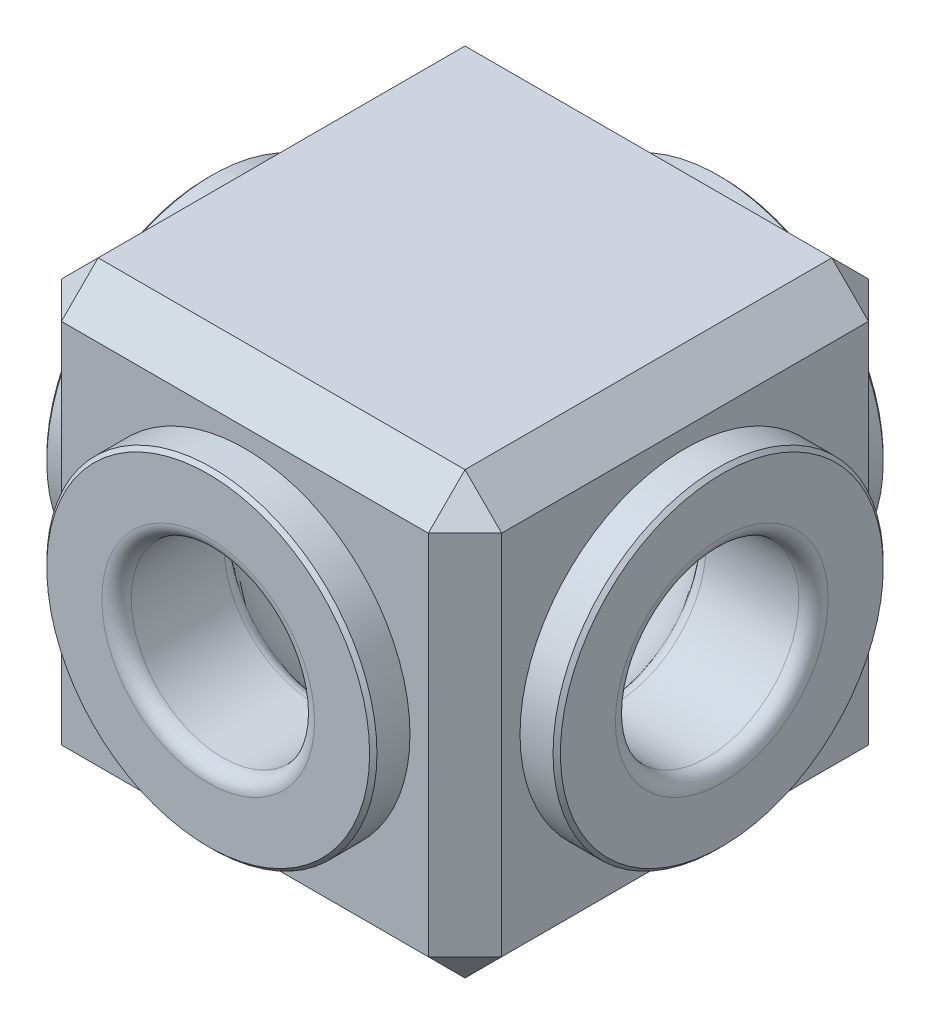
SolidWorks part; units mm, degrees
material "鉻不鏽鋼"
ref_plane "前基準面" through (0, 0, 0) normal (0, 0, 1) x (1, 0, 0)
ref_plane "上基準面" through (0, 0, 0) normal (0, 1, 0) x (1, 0, 0)
ref_plane "右基準面" through (0, 0, 0) normal (1, 0, 0) x (0, 0, -1)
sketch "草圖1" plane through (0, 0, 0) normal (0, 1, 0) x (1, 0, 0)
  line L1 (-30, -30) -> (30, -30)
  line L2 (-30, -30) -> (-30, 30)
  line L3 (-30, 30) -> (30, 30)
  line L4 (30, -30) -> (30, 30)
  line L5 (-30, -30) -> (30, 30) construction
  line L6 (-30, 30) -> (30, -30) construction
  point P0 (0, 0)
  dimension "D1" = 60
extrude "填料-伸長1" add sketch "草圖1" along normal mid plane 60
sketch "草圖2" plane through (0, 0, 0) normal (1, 0, 0) x (0, 0, -1)
  line L0 (0, -1001.1999) -> (0, 48998.8001) construction
  line L1 (-30, 30) -> (30, 30) construction
  line L2 (0, 23) -> (0, -23)
  arc A0 (0, -23) -> (0, 23) centre (0, 0) ccw
  dimension "D1" = 7
revolve "除料-旋轉1" cut sketch "草圖2" angle 360 about L0
sketch "草圖3" plane through (0, 0, 30) normal (0, 0, 1) x (1, 0, 0)
  circle A0 centre (0, 0) radius 12.5
  dimension "D1" = 25
extrude "除料-伸長1" cut sketch "草圖3" against normal through all
sketch "草圖4" plane through (30, 0, 0) normal (1, 0, 0) x (0, 0, -1)
  circle A0 centre (0, 0) radius 12.5
  dimension "D1" = 25
extrude "除料-伸長2" cut sketch "草圖4" against normal through all
sketch "草圖5" plane through (0, 0, 30) normal (0, 0, 1) x (1, 0, 0)
  circle A0 centre (0, 0) radius 12.5
  circle A1 centre (0, 0) radius 22.5
  dimension "D1" = 25
  dimension "D2" = 45
extrude "填料-伸長2" add sketch "草圖5" along normal blind 5
pattern_circular "環狀複製排列1" count 4 over 360 about axis through (0, 0, 0) along (0, 1, 0) of "填料-伸長2"
chamfer "導角1" distance 0.5 angle 45 4 edges at (-35, 0, 22.5) (-22.5, 0, -35) (35, 0, -22.5) (22.5, 0, 35)
fillet "圓角1" radius 2 8 edges at (19.3067, 0, 12.5) (-19.3067, 0, -12.5) (-12.5, 0, 19.3067) (12.5, 0, -19.3067) (-35, 0, 12.5) (-12.5, 0, -35) (35, 0, -12.5) (12.5, 0, 35)
chamfer "導角2" distance 5 angle 45 12 edges at (0, -30, -30) (-30, -30, 0) (0, -30, 30) (30, -30, 0) (0, 30, 30) (-30, 0, 30) (-30, 30, 0) (-30, 0, -30) (0, 30, -30) (30, 0, -30) (30, 30, 0) (30, 0, 30)
